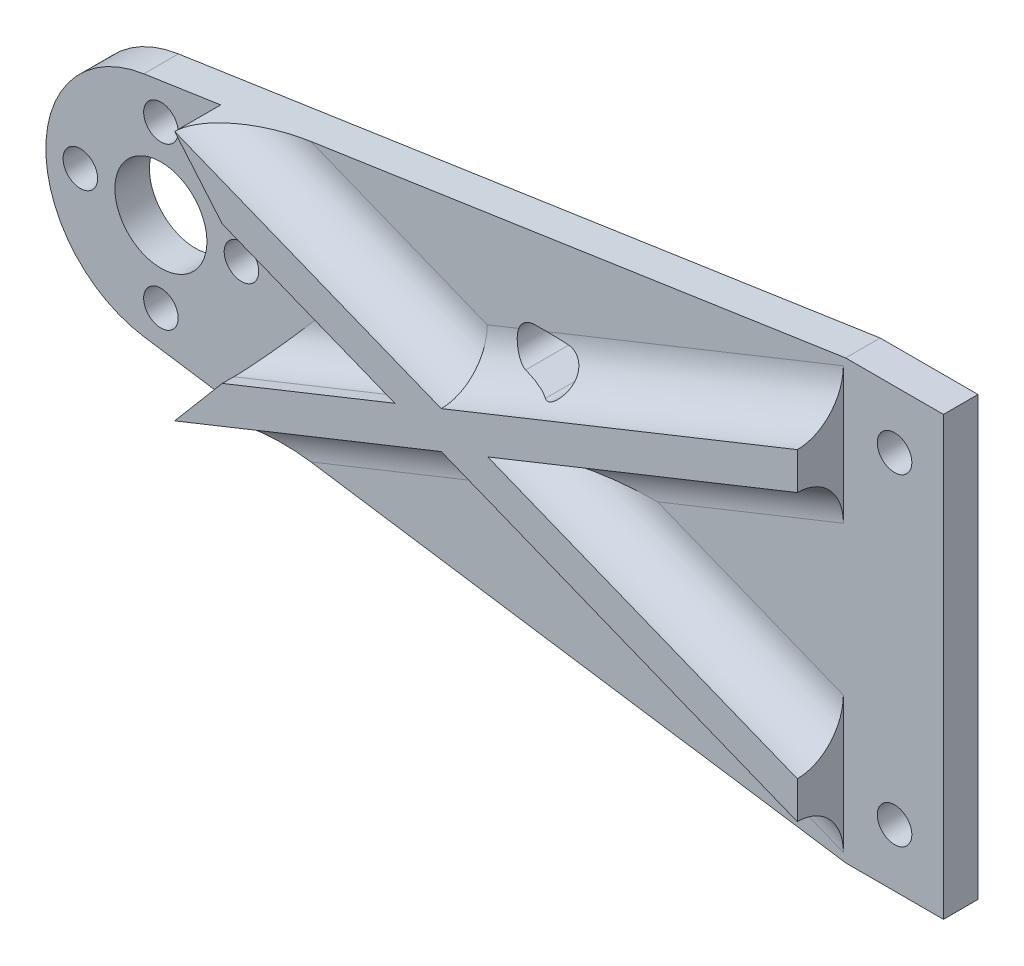
SolidWorks part; units mm, degrees
ref_plane "Спереди" through (0, 0, 0) normal (0, 0, 1) x (1, 0, 0)
ref_plane "Сверху" through (0, 0, 0) normal (0, 1, 0) x (1, 0, 0)
ref_plane "Справа" through (0, 0, 0) normal (1, 0, 0) x (0, 0, -1)
sketch "Sketch1" plane through (0, 0, 0) normal (0, 0, 1) x (1, 0, 0)
  line L4 (0, 0) -> (68, 0) construction
  line L6 (59.5, -19) -> (68, -19)
  line L8 (59.5, 19) -> (68, 19)
  line L9 (68, -19) -> (68, 19)
  line L10 (-1.4776, -9.8902) -> (59.5, -19)
  line L11 (-1.4776, 9.8902) -> (59.5, 19)
  arc A5 (-1.4776, 9.8902) -> (-1.4776, -9.8902) centre (0, 0) ccw
  circle A7 centre (0, 0) radius 4
  circle A8 centre (7, 0) radius 1.5
  circle A10 centre (0, -7) radius 1.5
  circle A12 centre (-7, 0) radius 1.5
  circle A14 centre (0, 7) radius 1.5
  circle A16 centre (-4.9497, 4.9497) radius 1.5 [skipped]
  circle A17 centre (-4.9497, -4.9497) radius 1.5 [skipped]
  circle A22 centre (4.9497, 4.9497) radius 1.5 [skipped]
  circle A23 centre (4.9497, -4.9497) radius 1.5 [skipped]
  circle A24 centre (63.75, -14) radius 1.5
  circle A25 centre (63.75, 14) radius 1.5
  point P9 (68, 0)
  point P11 (-10, 0)
  point P22 (63.75, -19)
  point P37 (0, 0)
  dimension "D4" = 38
  dimension "D11" = 10
  dimension "D12" = 8
  dimension "D13" = 7
  dimension "D14" = 3
  dimension "D17" = 5
  dimension "D6" = 3
  dimension "D8" = 3
  dimension "D7" = 10
  dimension "D9" = 5
  dimension "D10" = 68
  dimension "D16" = 7
  dimension "D5" = 8.5
  dimension "D15" = 8
extrude "плата" add sketch "Sketch1" along normal blind 3
sketch "Sketch3" plane through (0, 0, 0) normal (0, 0, -1) x (-1, 0, 0)
  line L0 (-35.5, -6.5) -> (-32.5, -6.5) construction
  line L1 (-35.5, -5) -> (-32.5, -5)
  line L2 (-35.5, -8) -> (-32.5, -8)
  line L3 (0, 0) -> (-68, 0) construction
  line L4 (-68, -19) -> (-68, 19) construction
  line L5 (-35.5, 6.5) -> (-32.5, 6.5) construction
  line L6 (-35.5, 5) -> (-32.5, 5)
  line L7 (-35.5, 8) -> (-32.5, 8)
  arc A0 (-35.5, -5) -> (-35.5, -8) centre (-35.5, -6.5) ccw
  arc A1 (-32.5, -8) -> (-32.5, -5) centre (-32.5, -6.5) ccw
  arc A2 (-35.5, 5) -> (-35.5, 8) centre (-35.5, 6.5) cw
  arc A3 (-32.5, 8) -> (-32.5, 5) centre (-32.5, 6.5) cw
  point P2 (-34, -6.5)
  point P13 (-68, 0)
  point P15 (-37, -6.5)
  point P16 (-31, -6.5)
  point P18 (-34, 0)
  point P21 (-34, 6.5)
  dimension "D1" = 3
  dimension "D2" = 6
  dimension "D3" = 5
extrude "Extrude3" cut sketch "Sketch3" against normal through all
sketch "Sketch5" plane through (0, 0, 3) normal (0, 0, 1) x (1, 0, 0)
  line L1 (9.3329, -6) -> (24.323, 0)
  line L2 (5.196, -10.8872) -> (28.3596, -1.6157)
  line L3 (59.3, 14) -> (59.3, 10.7686)
  line L8 (68, -19) -> (68, 19) construction
  line L9 (59.5, -19) -> (68, -19) construction
  line L10 (-1.4776, -9.8902) -> (59.5, -19) construction
  line L11 (68, 0) -> (-10, 0) construction
  line L12 (5.196, 10.8872) -> (28.3596, 1.6157)
  line L13 (59.3, -14) -> (59.3, -10.7686)
  line L14 (9.3329, 6) -> (24.323, 0)
  line L16 (32.3962, 0) -> (59.3, 10.7686)
  line L17 (28.3596, -1.6157) -> (59.3, -14)
  line L18 (32.3962, 0) -> (59.3, -10.7686)
  line L19 (28.3596, 1.6157) -> (59.3, 14)
  line L20 (59.5, 19) -> (-1.4776, 9.8902) construction
  line L22 (9.3329, -6) -> (5.196, -10.8872)
  line L23 (9.3329, 6) -> (5.196, 10.8872)
  arc A1 (-1.4776, 9.8902) -> (-1.4776, -9.8902) centre (0, 0) ccw construction
  circle A2 centre (0, 0) radius 10 construction
  dimension "D6" = 20
  dimension "D3" = 11
  dimension "D1" = 3
  dimension "D2" = 8.7
  dimension "D4" = 5
  dimension "D7" = 12
extrude "Extrude5" add sketch "Sketch5" along normal blind 4
fillet "Fillet2" radius 4 6 edges at (16.7778, 6.2515, 3) (43.8298, 7.8078, 3) (45.8481, 5.3843, 3) (45.8481, -5.3843, 3) (43.8298, -7.8078, 3) (16.7778, -6.2515, 3)
fillet "Fillet3" radius 3 2 edges at (16.828, -3, 3) (16.828, 3, 3)
